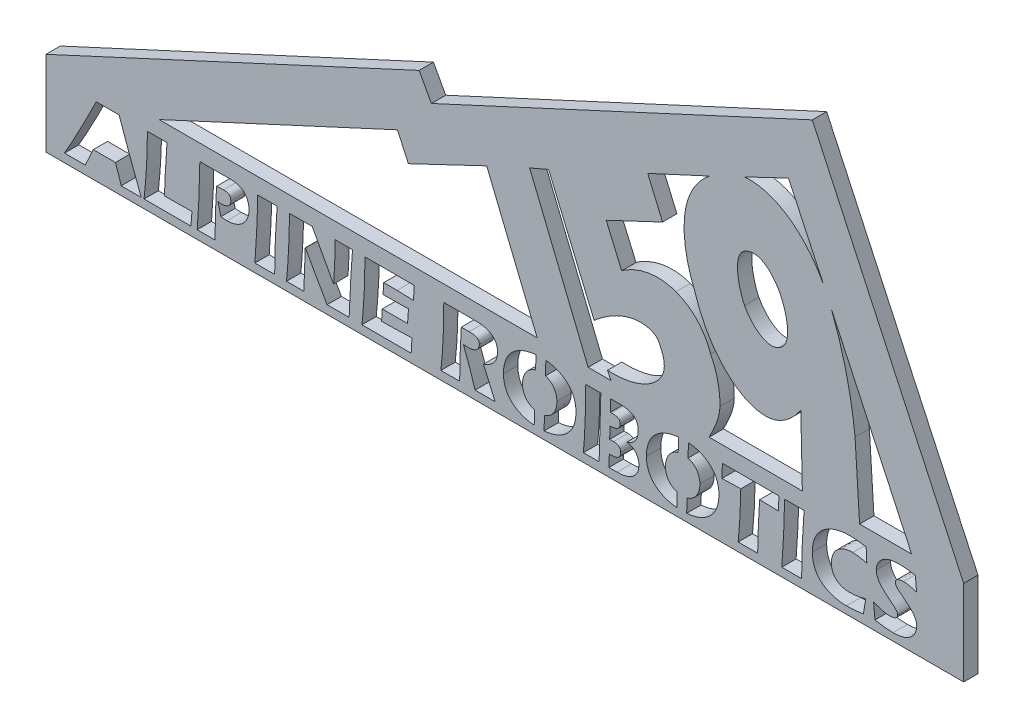
SolidWorks part; units mm, degrees
material "ABS PC"
ref_plane "Front Plane" through (0, 0, 0) normal (0, 0, 1) x (1, 0, 0)
ref_plane "Top Plane" through (0, 0, 0) normal (0, 1, 0) x (1, 0, 0)
ref_plane "Right Plane" through (0, 0, 0) normal (1, 0, 0) x (0, 0, -1)
sketch "Sketch3" plane through (0, 0, 0) normal (0, 0, 1) x (1, 0, 0)
  line L0 (55.8761, 162.9371) -> (53.3941, 170.5886)
  line L1 (49.7914, 162.9371) -> (55.8761, 162.9371)
  line L2 (53.3941, 170.5886) -> (49.7914, 162.9371)
  line L3 (244.0685, 183.4311) -> (221.6731, 238.2203)
  line L4 (221.6731, 238.2203) -> (186.9968, 221.7135)
  line L5 (227.5281, 183.4311) -> (244.0685, 183.4311)
  line L6 (76.5606, 183.4311) -> (204.5657, 183.4311)
  line L7 (204.5657, 183.4311) -> (227.5281, 183.4311)
  line L8 (182.1485, 232.278) -> (186.9968, 221.7135)
  line L9 (182.1485, 232.278) -> (76.5606, 183.4311)
  line L10 (412.0616, 169.7868) -> (411.5399, 176.0764)
  line L11 (393.033, 156.6464) -> (393.6346, 150.0362)
  line L12 (390.0186, 170.0274) -> (389.7375, 176.1169)
  line L13 (388.4928, 149.7562) -> (389.5362, 156.0863)
  line L14 (362.2364, 176.3575) -> (353.5244, 176.3575)
  line L15 (352.3606, 149.6359) -> (361.1524, 149.6359)
  line L16 (351.1137, 176.3575) -> (326.0626, 176.3575)
  line L17 (326.0626, 176.3575) -> (325.8614, 170.4278)
  line L18 (333.0476, 149.6359) -> (341.6787, 149.6359)
  line L19 (350.872, 170.4278) -> (351.1137, 176.3575)
  line L20 (311.0283, 176.744) -> (310.8568, 170.723)
  line L21 (310.4167, 155.2717) -> (310.2451, 149.2475)
  line L22 (306.4927, 170.6747) -> (306.6646, 176.7103)
  line L23 (305.8831, 149.2731) -> (306.0551, 155.3102)
  line L24 (275.982, 154.8842) -> (275.8324, 149.6359)
  line L25 (275.8324, 149.6359) -> (279.4445, 149.6359)
  line L26 (283.8207, 163.297) -> (283.8207, 163.3768)
  line L27 (280.9703, 176.3575) -> (276.5936, 176.3575)
  line L28 (276.5936, 176.3575) -> (276.4441, 171.1093)
  line L29 (276.4441, 171.1093) -> (276.9561, 171.1093)
  line L30 (276.3939, 165.8205) -> (276.2935, 165.8205)
  line L31 (276.2935, 165.8205) -> (276.144, 160.5733)
  line L32 (276.144, 160.5733) -> (277.8793, 160.5733)
  line L33 (276.5547, 154.8842) -> (275.982, 154.8842)
  line L34 (271.4698, 149.6359) -> (272.2309, 176.3575)
  line L35 (272.2309, 176.3575) -> (265.5545, 176.3575)
  line L36 (264.4705, 149.6359) -> (271.4698, 149.6359)
  line L37 (247.8705, 176.7278) -> (247.6983, 170.6839)
  line L38 (247.2606, 155.3147) -> (247.0882, 149.2639)
  line L39 (243.3365, 170.7163) -> (243.5077, 176.7246)
  line L40 (242.7253, 149.2583) -> (242.8966, 155.2733)
  line L41 (216.8515, 176.3575) -> (202.6798, 176.3575)
  line L42 (201.3951, 149.6359) -> (209.7052, 149.6359)
  line L43 (210.4282, 170.7483) -> (213.8807, 170.7483)
  line L44 (216.5299, 149.6359) -> (225.4426, 149.6359)
  line L45 (189.5569, 176.3575) -> (167.7811, 176.3575)
  line L46 (166.4204, 149.6359) -> (188.2361, 149.6359)
  line L47 (188.2361, 149.6359) -> (188.596, 155.6849)
  line L48 (177.7885, 155.3644) -> (175.1462, 155.3644)
  line L49 (175.1462, 155.3644) -> (175.4268, 160.2123)
  line L50 (175.4268, 160.2123) -> (186.6346, 160.2123)
  line L51 (186.6346, 160.2123) -> (187.035, 166.0611)
  line L52 (180.3503, 165.9408) -> (175.7867, 165.9408)
  line L53 (175.7867, 165.9408) -> (176.0673, 170.629)
  line L54 (176.0673, 170.629) -> (181.9917, 170.629)
  line L55 (189.2769, 170.3884) -> (189.5569, 176.3575)
  line L56 (162.2501, 176.3575) -> (154.605, 176.3575)
  line L57 (153.9241, 159.0506) -> (153.8443, 159.0506)
  line L58 (153.8443, 159.0506) -> (144.3975, 176.3575)
  line L59 (144.3975, 176.3575) -> (134.3902, 176.3575)
  line L60 (133.0294, 149.6359) -> (140.715, 149.6359)
  line L61 (141.315, 166.6223) -> (141.3954, 166.6223)
  line L62 (151.0024, 149.6359) -> (160.7696, 149.6359)
  line L63 (128.864, 176.3575) -> (120.1775, 176.3575)
  line L64 (119.0169, 149.6359) -> (127.7833, 149.6359)
  line L65 (108.8046, 176.3575) -> (94.6346, 176.3575)
  line L66 (93.474, 149.6359) -> (101.3996, 149.6359)
  line L67 (102.6806, 165.0602) -> (103.9615, 159.8918)
  line L68 (90.7071, 149.6359) -> (91.1474, 155.4847)
  line L69 (83.4618, 155.3644) -> (78.9786, 155.3644)
  line L70 (80.0993, 176.3575) -> (71.4533, 176.3575)
  line L71 (69.9322, 149.6359) -> (90.7071, 149.6359)
  line L72 (58.8782, 176.3575) -> (48.791, 176.3575)
  line L73 (34.7008, 149.6359) -> (43.9074, 149.6359)
  line L74 (43.9074, 149.6359) -> (47.4297, 157.3278)
  line L75 (47.4297, 157.3278) -> (57.2768, 157.3278)
  line L76 (59.7987, 149.6359) -> (68.6854, 149.6359)
  line L77 (355.3479, 300.3693) -> (335.8627, 291.0793)
  line L78 (370.811, 267.357) -> (355.3479, 300.3693)
  line L79 (240.6994, 246.9321) -> (266.5948, 183.4311)
  line L80 (266.5948, 183.4311) -> (276.7567, 183.4311)
  line L81 (276.7567, 183.4311) -> (275.1539, 186.5494)
  line L82 (249.0949, 250.5738) -> (240.6994, 246.9321)
  line L83 (320.1629, 183.4311) -> (361.4756, 183.4311)
  line L84 (361.4756, 183.4311) -> (360.7887, 214.0367)
  line L85 (320.4246, 283.7091) -> (318.8, 282.9349)
  line L86 (318.8, 282.9349) -> (292.9917, 270.9958)
  line L87 (292.9917, 270.9958) -> (299.5774, 255.6221)
  line L88 (299.5774, 255.6221) -> (274.5978, 243.8247)
  line L89 (274.5978, 243.8247) -> (281.4669, 227.8949)
  line L90 (409.8755, 183.4311) -> (374.3088, 259.6999)
  line L91 (386.8258, 183.4311) -> (409.8755, 183.4311)
  line L92 (432.9143, 145.8909) -> (432.9143, 183.7037)
  line L93 (26.5143, 145.8909) -> (432.9143, 145.8909)
  line L94 (26.5143, 183.4311) -> (26.5143, 145.8909)
  line L95 (191.7543, 259.8743) -> (26.5143, 183.4311)
  line L96 (197.1951, 249.9087) -> (191.7543, 259.8743)
  line L97 (365.8806, 327.9657) -> (197.1951, 249.9087)
  line L98 (432.9143, 183.7037) -> (365.8806, 327.9657)
  spline S0 degree 3 poles (402.6277, 168.9861) (402.6277, 170.6684) (404.9958, 171.1093) (406.2405, 171.1093) knots 0 0 0 0 1 1 1 1
  spline S1 degree 3 poles (406.2405, 171.1093) (408.2082, 171.1093) (410.2547, 170.5087) (412.0616, 169.7868) knots 0 0 0 0 1 1 1 1
  spline S2 degree 3 poles (411.5399, 176.0764) (409.2112, 176.5173) (406.8027, 176.8378) (404.3942, 176.8378) knots 0 0 0 0 1 1 1 1
  spline S3 degree 3 poles (404.3942, 176.8378) (395.2807, 176.8378) (394.1968, 171.3499) (394.1968, 169.5068) knots 0 0 0 0 1 1 1 1
  spline S4 degree 3 poles (394.1968, 169.5068) (394.1968, 163.2565) (403.7116, 160.0515) (403.7116, 156.9669) knots 0 0 0 0 1 1 1 1
  spline S5 degree 3 poles (403.7116, 156.9669) (403.7116, 155.1248) (401.2627, 154.8842) (399.9381, 154.8842) knots 0 0 0 0 1 1 1 1
  spline S6 degree 3 poles (399.9381, 154.8842) (397.6094, 154.8842) (395.1199, 155.7253) (393.033, 156.6464) knots 0 0 0 0 1 1 1 1
  spline S7 degree 3 poles (393.6346, 150.0362) (396.2444, 149.556) (398.934, 149.1546) (401.6236, 149.1546) knots 0 0 0 0 1 1 1 1
  spline S8 degree 3 poles (401.6236, 149.1546) (410.2153, 149.1546) (412.1415, 154.2027) (412.1415, 156.9275) knots 0 0 0 0 1 1 1 1
  spline S9 degree 3 poles (412.1415, 156.9275) (412.1415, 162.8561) (402.6277, 165.8205) (402.6277, 168.9861) knots 0 0 0 0 1 1 1 1
  spline S10 degree 3 poles (383.7556, 170.9889) (385.883, 170.9889) (387.971, 170.5087) (390.0186, 170.0274) knots 0 0 0 0 1 1 1 1
  spline S11 degree 3 poles (389.7375, 176.1169) (387.3684, 176.5173) (384.9598, 176.8378) (382.5513, 176.8378) knots 0 0 0 0 1 1 1 1
  spline S12 degree 3 poles (382.5513, 176.8378) (373.5188, 176.8378) (365.8907, 171.9909) (365.8907, 162.2556) knots 0 0 0 0 1 1 1 1
  spline S13 degree 3 poles (365.8907, 162.2556) (365.8907, 151.7995) (374.723, 149.1546) (381.0255, 149.1546) knots 0 0 0 0 1 1 1 1
  spline S14 degree 3 poles (381.0255, 149.1546) (383.5149, 149.1546) (386.0438, 149.3952) (388.4928, 149.7562) knots 0 0 0 0 1 1 1 1
  spline S15 degree 3 poles (389.5362, 156.0863) (387.2076, 155.4847) (384.8395, 155.0045) (382.3905, 155.0045) knots 0 0 0 0 1 1 1 1
  spline S16 degree 3 poles (382.3905, 155.0045) (377.8141, 155.0045) (374.3216, 157.4481) (374.3216, 162.3355) knots 0 0 0 0 1 1 1 1
  spline S17 degree 3 poles (374.3216, 162.3355) (374.3216, 166.3422) (376.9708, 170.9889) (383.7556, 170.9889) knots 0 0 0 0 1 1 1 1
  spline S18 degree 3 poles (361.1524, 149.6359) (361.1929, 158.53) (361.5134, 167.4634) (362.2364, 176.3575) knots 0 0 0 0 1 1 1 1
  spline S19 degree 3 poles (353.5244, 176.3575) (353.5244, 165.4606) (352.8823, 157.528) (352.3606, 149.6359) knots 0 0 0 0 1 1 1 1
  spline S20 degree 3 poles (325.8614, 170.4278) (328.6724, 170.5087) (331.4419, 170.629) (334.2125, 170.629) knots 0 0 0 0 1 1 1 1
  spline S21 degree 3 poles (334.2125, 170.629) (334.1315, 162.5357) (333.6897, 156.0458) (333.0476, 149.6359) knots 0 0 0 0 1 1 1 1
  spline S22 degree 3 poles (341.6787, 149.6359) (341.7192, 154.6435) (342.0801, 164.2585) (342.5625, 170.629) knots 0 0 0 0 1 1 1 1
  spline S23 degree 3 poles (342.5625, 170.629) (345.6535, 170.629) (350.5515, 170.4683) (350.872, 170.4278) knots 0 0 0 0 1 1 1 1
  spline S24 degree 3 poles (310.2451, 149.2475) (318.3651, 149.9174) (324.5315, 154.6275) (324.5315, 163.6175) knots 0 0 0 0 1 1 1 1
  spline S25 degree 3 poles (324.5315, 163.6175) (324.5315, 171.8331) (318.3842, 176.1077) (311.0283, 176.744) knots 0 0 0 0 1 1 1 1
  spline S26 degree 3 poles (310.8568, 170.723) (314.0861, 169.8742) (316.1016, 167.0255) (316.1016, 163.4173) knots 0 0 0 0 1 1 1 1
  spline S27 degree 3 poles (316.1016, 163.4173) (316.1016, 159.5472) (313.9906, 156.2045) (310.4167, 155.2717) knots 0 0 0 0 1 1 1 1
  spline S28 degree 3 poles (306.0551, 155.3102) (302.9025, 156.1899) (300.8466, 158.9028) (300.8466, 162.4963) knots 0 0 0 0 1 1 1 1
  spline S29 degree 3 poles (300.8466, 162.4963) (300.8466, 166.4283) (302.9629, 169.6874) (306.4927, 170.6747) knots 0 0 0 0 1 1 1 1
  spline S30 degree 3 poles (306.6646, 176.7103) (299.5921, 176.0167) (292.4156, 172.1382) (292.4156, 162.2152) knots 0 0 0 0 1 1 1 1
  spline S31 degree 3 poles (292.4156, 162.2152) (292.4156, 153.9462) (298.6053, 149.9567) (305.8831, 149.2731) knots 0 0 0 0 1 1 1 1
  spline S32 degree 3 poles (279.4445, 149.6359) (285.4669, 149.6359) (289.0797, 152.3596) (289.0797, 157.1681) knots 0 0 0 0 1 1 1 1
  spline S33 degree 3 poles (289.0797, 157.1681) (289.0797, 160.4923) (286.9523, 162.9371) (283.8207, 163.297) knots 0 0 0 0 1 1 1 1
  spline S34 degree 3 poles (283.8207, 163.3768) (287.0321, 164.2191) (288.7986, 166.6627) (288.7986, 170.1478) knots 0 0 0 0 1 1 1 1
  spline S35 degree 3 poles (288.7986, 170.1478) (288.7986, 174.7146) (285.5467, 176.3575) (280.9703, 176.3575) knots 0 0 0 0 1 1 1 1
  spline S36 degree 3 poles (276.9561, 171.1093) (278.6821, 171.1093) (280.7297, 170.9485) (280.7297, 168.7454) knots 0 0 0 0 1 1 1 1
  spline S37 degree 3 poles (280.7297, 168.7454) (280.7297, 166.7831) (279.485, 165.8205) (276.3939, 165.8205) knots 0 0 0 0 1 1 1 1
  spline S38 degree 3 poles (277.8793, 160.5733) (280.1675, 160.5733) (281.0108, 159.4105) (281.0108, 157.9284) knots 0 0 0 0 1 1 1 1
  spline S39 degree 3 poles (281.0108, 157.9284) (281.0108, 155.1642) (278.7226, 154.8842) (276.5547, 154.8842) knots 0 0 0 0 1 1 1 1
  spline S40 degree 3 poles (265.5545, 176.3575) (265.5949, 168.6656) (265.0732, 153.9227) (264.4705, 149.6359) knots 0 0 0 0 1 1 1 1
  spline S41 degree 3 poles (247.0882, 149.2639) (255.1282, 149.9828) (261.2144, 154.6872) (261.2144, 163.6175) knots 0 0 0 0 1 1 1 1
  spline S42 degree 3 poles (261.2144, 163.6175) (261.2144, 171.7735) (255.1553, 176.0435) (247.8705, 176.7278) knots 0 0 0 0 1 1 1 1
  spline S43 degree 3 poles (247.6983, 170.6839) (250.8362, 169.7852) (252.7846, 166.9669) (252.7846, 163.4173) knots 0 0 0 0 1 1 1 1
  spline S44 degree 3 poles (252.7846, 163.4173) (252.7846, 159.6055) (250.7369, 156.3049) (247.2606, 155.3147) knots 0 0 0 0 1 1 1 1
  spline S45 degree 3 poles (242.8966, 155.2733) (239.6561, 156.1061) (237.5295, 158.8439) (237.5295, 162.4963) knots 0 0 0 0 1 1 1 1
  spline S46 degree 3 poles (237.5295, 162.4963) (237.5295, 166.4874) (239.7106, 169.7841) (243.3365, 170.7163) knots 0 0 0 0 1 1 1 1
  spline S47 degree 3 poles (243.5077, 176.7246) (236.3838, 176.0742) (229.0986, 172.2132) (229.0986, 162.2152) knots 0 0 0 0 1 1 1 1
  spline S48 degree 3 poles (229.0986, 162.2152) (229.0986, 153.8859) (235.3786, 149.8981) (242.7253, 149.2583) knots 0 0 0 0 1 1 1 1
  spline S49 degree 3 poles (225.4426, 149.6359) (223.7566, 153.6022) (221.7894, 157.4481) (220.2236, 161.4538) knots 0 0 0 0 1 1 1 1
  spline S50 degree 3 poles (220.2236, 161.4538) (223.9972, 162.7763) (226.4861, 165.0602) (226.4861, 169.2661) knots 0 0 0 0 1 1 1 1
  spline S51 degree 3 poles (226.4861, 169.2661) (226.4861, 176.1574) (218.7782, 176.3575) (216.8515, 176.3575) knots 0 0 0 0 1 1 1 1
  spline S52 degree 3 poles (202.6798, 176.3575) (202.6399, 165.6608) (202.3188, 157.9284) (201.3951, 149.6359) knots 0 0 0 0 1 1 1 1
  spline S53 degree 3 poles (209.7052, 149.6359) (209.7856, 156.6868) (209.9863, 163.7378) (210.4282, 170.7483) knots 0 0 0 0 1 1 1 1
  spline S54 degree 3 poles (213.8807, 170.7483) (215.7271, 170.7483) (218.4167, 170.7483) (218.4167, 168.065) knots 0 0 0 0 1 1 1 1
  spline S55 degree 3 poles (218.4167, 168.065) (218.4167, 165.2998) (215.6467, 164.4192) (213.3185, 164.4192) knots 0 0 0 0 1 1 1 1
  spline S56 degree 3 poles (213.3185, 164.4192) (212.6759, 164.4192) (211.9934, 164.4991) (211.3514, 164.6194) knots 0 0 0 0 1 1 1 1
  spline S57 degree 3 poles (211.3514, 164.6194) (213.1982, 159.6512) (215.085, 154.7234) (216.5299, 149.6359) knots 0 0 0 0 1 1 1 1
  spline S58 degree 3 poles (167.7811, 176.3575) (167.7811, 163.4577) (166.9006, 154.043) (166.4204, 149.6359) knots 0 0 0 0 1 1 1 1
  spline S59 degree 3 poles (188.596, 155.6849) (184.9938, 155.4847) (181.3911, 155.3644) (177.7885, 155.3644) knots 0 0 0 0 1 1 1 1
  spline S60 degree 3 poles (187.035, 166.0611) (184.7936, 165.9813) (182.5917, 165.9408) (180.3503, 165.9408) knots 0 0 0 0 1 1 1 1
  spline S61 degree 3 poles (181.9917, 170.629) (184.3933, 170.629) (186.8348, 170.5087) (189.2769, 170.3884) knots 0 0 0 0 1 1 1 1
  spline S62 degree 3 poles (160.7696, 149.6359) (160.8894, 156.6464) (162.01, 173.6328) (162.2501, 176.3575) knots 0 0 0 0 1 1 1 1
  spline S63 degree 3 poles (154.605, 176.3575) (154.605, 171.6704) (154.1243, 161.6146) (153.9241, 159.0506) knots 0 0 0 0 1 1 1 1
  spline S64 degree 3 poles (134.3902, 176.3575) (134.3902, 168.6656) (133.5496, 153.8822) (133.0294, 149.6359) knots 0 0 0 0 1 1 1 1
  spline S65 degree 3 poles (140.715, 149.6359) (140.715, 153.6416) (141.1952, 164.2191) (141.315, 166.6223) knots 0 0 0 0 1 1 1 1
  spline S66 degree 3 poles (141.3954, 166.6223) (144.2373, 160.9736) (147.9198, 155.4453) (151.0024, 149.6359) knots 0 0 0 0 1 1 1 1
  spline S67 degree 3 poles (127.7833, 149.6359) (127.8232, 158.53) (128.1432, 167.4634) (128.864, 176.3575) knots 0 0 0 0 1 1 1 1
  spline S68 degree 3 poles (120.1775, 176.3575) (120.1775, 165.4606) (119.5371, 157.528) (119.0169, 149.6359) knots 0 0 0 0 1 1 1 1
  spline S69 degree 3 poles (94.6346, 176.3575) (94.6346, 168.6656) (93.9142, 153.682) (93.474, 149.6359) knots 0 0 0 0 1 1 1 1
  spline S70 degree 3 poles (101.3996, 149.6359) (101.3996, 159.6512) (101.7196, 164.4586) (102.0401, 170.5886) knots 0 0 0 0 1 1 1 1
  spline S71 degree 3 poles (102.0401, 170.5886) (103.0809, 170.6684) (104.0813, 170.7483) (105.1221, 170.7483) knots 0 0 0 0 1 1 1 1
  spline S72 degree 3 poles (105.1221, 170.7483) (106.9636, 170.7483) (108.3644, 170.3479) (108.3644, 168.1843) knots 0 0 0 0 1 1 1 1
  spline S73 degree 3 poles (108.3644, 168.1843) (108.3644, 165.7811) (106.4829, 164.8995) (104.3214, 164.8995) knots 0 0 0 0 1 1 1 1
  spline S74 degree 3 poles (104.3214, 164.8995) (103.7613, 164.8995) (103.2007, 164.9793) (102.6806, 165.0602) knots 0 0 0 0 1 1 1 1
  spline S75 degree 3 poles (103.9615, 159.8918) (104.8421, 159.7321) (105.7226, 159.6512) (106.6431, 159.6512) knots 0 0 0 0 1 1 1 1
  spline S76 degree 3 poles (106.6431, 159.6512) (112.0874, 159.6512) (116.4104, 163.0563) (116.4104, 168.7454) knots 0 0 0 0 1 1 1 1
  spline S77 degree 3 poles (116.4104, 168.7454) (116.4104, 171.1891) (115.3695, 176.3575) (108.8046, 176.3575) knots 0 0 0 0 1 1 1 1
  spline S78 degree 3 poles (91.1474, 155.4847) (88.5856, 155.3644) (86.0237, 155.3644) (83.4618, 155.3644) knots 0 0 0 0 1 1 1 1
  spline S79 degree 3 poles (78.9786, 155.3644) (79.0989, 161.6551) (79.8991, 173.6732) (80.0993, 176.3575) knots 0 0 0 0 1 1 1 1
  spline S80 degree 3 poles (71.4533, 176.3575) (71.3729, 167.4241) (70.9326, 158.4895) (69.9322, 149.6359) knots 0 0 0 0 1 1 1 1
  spline S81 degree 3 poles (68.6854, 149.6359) (65.2829, 158.4895) (61.9602, 167.3836) (58.8782, 176.3575) knots 0 0 0 0 1 1 1 1
  spline S82 degree 3 poles (48.791, 176.3575) (46.5891, 171.6704) (37.5427, 154.323) (34.7008, 149.6359) knots 0 0 0 0 1 1 1 1
  spline S83 degree 3 poles (57.2768, 157.3278) (58.1978, 154.7638) (59.1183, 152.2403) (59.7987, 149.6359) knots 0 0 0 0 1 1 1 1
  spline S84 degree 3 poles (351.0477, 255.2795) (348.9891, 258.7792) (343.3758, 266.3721) (336.3626, 262.8966) knots 0 0 0 0 1 1 1 1
  spline S85 degree 3 poles (336.3626, 262.8966) (329.9121, 259.6999) (333.6403, 246.0744) (335.8627, 241.7609) knots 0 0 0 0 1 1 1 1
  spline S86 degree 3 poles (335.8627, 241.7609) (338.3526, 236.9283) (345.009, 229.8892) (351.0477, 233.1831) knots 0 0 0 0 1 1 1 1
  spline S87 degree 3 poles (351.0477, 233.1831) (358.8343, 237.4303) (352.9617, 252.0258) (351.0477, 255.2795) knots 0 0 0 0 1 1 1 1
  spline S88 degree 3 poles (335.8627, 291.0793) (348.3715, 292.2326) (361.9587, 283.7091) (370.811, 267.357) knots 0 0 0 0 1 1 1 1
  spline S89 degree 3 poles (275.1539, 186.5494) (288.4342, 185.8298) (298.3889, 191.5541) (300.0789, 198.6631) knots 0 0 0 0 1 1 1 1
  spline S90 degree 3 poles (300.0789, 198.6631) (300.4169, 200.0805) (300.7222, 202.8281) (298.8905, 206.677) knots 0 0 0 0 1 1 1 1
  spline S91 degree 3 poles (298.8905, 206.677) (298.0945, 208.8577) (297.0696, 210.286) (295.9466, 210.8857) knots 0 0 0 0 1 1 1 1
  spline S92 degree 3 poles (295.9466, 210.8857) (288.9467, 214.5819) (278.5122, 210.8312) (269.2552, 202.7409) knots 0 0 0 0 1 1 1 1
  spline S93 degree 3 poles (269.2552, 202.7409) (262.5278, 218.6816) (255.8114, 234.6332) (249.0949, 250.5738) knots 0 0 0 0 1 1 1 1
  spline S94 degree 3 poles (360.7887, 214.0367) (355.4352, 206.1754) (349.9508, 204.6817) (347.8901, 204.2892) knots 0 0 0 0 1 1 1 1
  spline S95 degree 3 poles (347.8901, 204.2892) (336.049, 202.0758) (320.4246, 214.5165) (313.5773, 236.9337) knots 0 0 0 0 1 1 1 1
  spline S96 degree 3 poles (313.5773, 236.9337) (313.0212, 238.1658) (302.5104, 262.4585) (315.638, 278.9552) knots 0 0 0 0 1 1 1 1
  spline S97 degree 3 poles (315.638, 278.9552) (316.7502, 280.3617) (318.3093, 282.0408) (320.4246, 283.7091) knots 0 0 0 0 1 1 1 1
  spline S98 degree 3 poles (281.4669, 227.8949) (282.1102, 228.4073) (292.7846, 236.4867) (305.5088, 231.8637) knots 0 0 0 0 1 1 1 1
  spline S99 degree 3 poles (305.5088, 231.8637) (316.9464, 227.7095) (320.4791, 216.7735) (320.8498, 215.5523) knots 0 0 0 0 1 1 1 1
  spline S100 degree 3 poles (320.8498, 215.5523) (322.3653, 212.8047) (325.1457, 206.2845) (324.9712, 197.5727) knots 0 0 0 0 1 1 1 1
  spline S101 degree 3 poles (324.9712, 197.5727) (324.884, 192.9497) (322.6488, 188.2503) (320.1629, 183.4311) knots 0 0 0 0 1 1 1 1
  spline S102 degree 3 poles (374.3088, 259.6999) (375.5082, 256.6252) (376.6531, 253.3978) (377.7216, 250.0177) knots 0 0 0 0 1 1 1 1
  spline S103 degree 3 poles (377.7216, 250.0177) (381.7122, 237.4898) (383.7838, 225.8777) (384.8088, 215.8249) knots 0 0 0 0 1 1 1 1
  spline S104 degree 3 poles (384.8088, 215.8249) (385.4848, 205.0197) (386.1498, 194.2254) (386.8258, 183.4311) knots 0 0 0 0 1 1 1 1
  dimension "D1" = 406.4
extrude "Boss-Extrude1" add sketch "Sketch3" along normal blind 6.35 contours L92 L98 L97 L96 L95 L94 L93 S104 S103 S102 L90 L91 S101 S100 S99 S98 L89 L88 L87 L86 L85 S97 S96 S95 S94 L84 L83 S93 S92 S91 S90 S89 L81 L80 L79 L82 S88 L77 L78 S87 S86 S85 S84 S83 L75 region at (268.652, 215.1763, 0)
